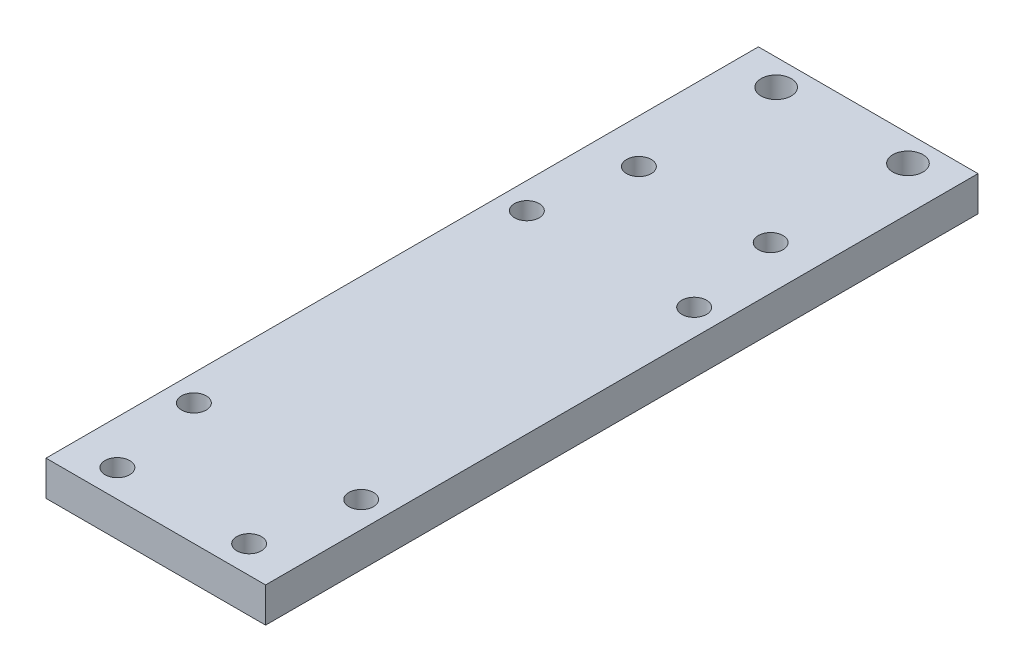
SolidWorks part; units mm, degrees
material "6061 Alloy"
ref_plane "Front Plane" through (0, 0, 0) normal (0, 0, 1) x (1, 0, 0)
ref_plane "Top Plane" through (0, 0, 0) normal (0, 1, 0) x (1, 0, 0)
ref_plane "Right Plane" through (0, 0, 0) normal (1, 0, 0) x (0, 0, -1)
sketch "Sketch1" plane through (0, 0, 0) normal (0, 1, 0) x (1, 0, 0)
  line L1 (-20, 80) -> (20, 80)
  line L2 (-20, 80) -> (-20, -80)
  line L3 (-20, -80) -> (20, -80)
  line L4 (20, 80) -> (20, -80)
  line L5 (0, -80) -> (0, 80) construction
  line L6 (-20, 0) -> (20, 0) construction
  point P0 (0, 0)
  dimension "D1" = 40
  dimension "D2" = 160
extrude "Boss-Extrude1" add sketch "Sketch1" along normal mid plane 6.35
sketch "Sketch3" plane through (0, 0, 0) normal (0, 1, 0) x (1, 0, 0)
  line L0 (0, 75.2375) -> (12, 75.2375) construction
  line L5 (0, -80) -> (0, 80) construction
  line L6 (-20, 0) -> (20, 0) construction
  line L7 (0, 50.2375) -> (12, 50.2375) construction
  line L8 (20, 80) -> (-20, 80) construction
  line L9 (-20, 80) -> (-20, -80) construction
  line L10 (-20, -80) -> (20, -80) construction
  line L11 (20, -80) -> (20, 80) construction
  circle A0 centre (12, 75.2375) radius 2.75
  circle A1 centre (12, 50.2375) radius 2.25
  circle A2 centre (-12, 50.2375) radius 2.25
  circle A3 centre (-12, 75.2375) radius 2.75
  circle A4 centre (-12, -44.7625) radius 2.25
  circle A5 centre (12, -44.7625) radius 2.25
  point P0 (0, 0)
  dimension "D4" = 5.5
  dimension "D5" = 4.5
  dimension "D1" = 4.7625
  dimension "D2" = 25
  dimension "D3" = 12
  dimension "D6" = 2
extrude "M4/5_through" cut sketch "Sketch3" against normal up to surface (3.175 mm away) and the other way blind 6.35 up to face at (0, -3.175, 0)
sketch "Sketch4" plane through (0, 0, -80) normal (0, 0, -1) x (-1, 0, 0)
  circle A0 centre (0, 0) radius 1.5
  dimension "D1" = 3
extrude "M3_DRILL" cut sketch "Sketch4" against normal blind 8
sketch "Sketch5" plane through (0, 3.175, 0) normal (0, 1, 0) x (1, 0, 0)
  line L0 (-12, -44.7625) -> (0, -44.7625) construction
  line L2 (0, 0) -> (0, -23.6676) construction
  line L3 (-12, 50.2375) -> (-12, -44.7625) construction
  line L4 (-12, 2.7375) -> (-1.1233, 2.7375) construction
  line L5 (-20, 80) -> (-20, -80) construction
  circle A0 centre (-15.2375, -27.5875) radius 2.25
  circle A1 centre (15.2375, -27.5875) radius 2.25
  circle A2 centre (15.2375, 33.0625) radius 2.25
  circle A3 centre (-15.2375, 33.0625) radius 2.25
  circle A4 centre (-12, -44.7625) radius 2.25 construction
  circle A6 centre (-12, 50.2375) radius 2.25 construction
  dimension "D2" = 4.5
  dimension "D1" = 17.175
  dimension "D3" = 4.7625
extrude "M4_through" cut sketch "Sketch5" against normal up to surface (6.35 mm away) up to face at (12, -3.175, 47.0125)
sketch "Sketch6" plane through (0, 3.175, 0) normal (0, 1, 0) x (1, 0, 0)
  line L0 (-12, -44.7625) -> (12, -44.7625) construction
  line L2 (20, -80) -> (20, 80) construction
  line L3 (-20, -80) -> (20, -80)
  line L4 (-20, -80) -> (-20, -49.7625)
  line L5 (-20, -49.7625) -> (20, -49.7625)
  line L6 (20, -80) -> (20, -49.7625)
  line L7 (0, -49.7625) -> (0, -80) construction
  line L8 (-20, -64.8812) -> (20, -64.8812) construction
  point P220 (0, -64.8812)
  dimension "D1" = 5
extrude "Cut-Extrude1" cut sketch "Sketch6" against normal up to surface (6.35 mm away) up to face at (-15.2375, -3.175, -30.8125)
